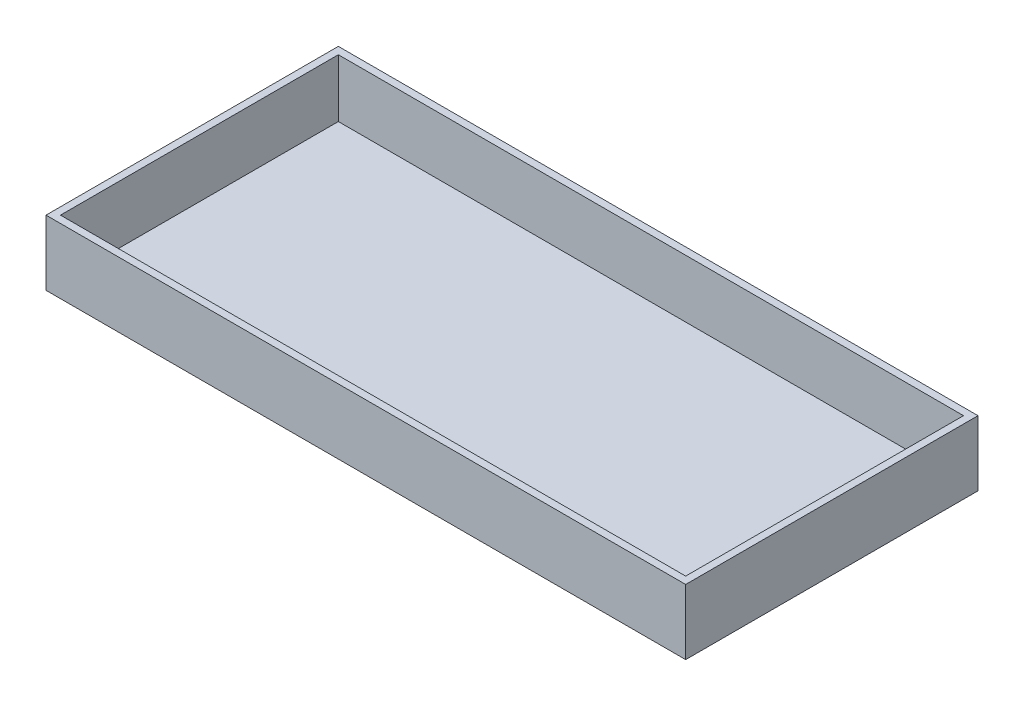
SolidWorks part; units mm, degrees
ref_plane "Front Plane" through (0, 0, 0) normal (0, 0, 1) x (1, 0, 0)
ref_plane "Top Plane" through (0, 0, 0) normal (0, 1, 0) x (1, 0, 0)
ref_plane "Right Plane" through (0, 0, 0) normal (1, 0, 0) x (0, 0, -1)
sketch "Sketch1" plane through (0, 0, 0) normal (0, 1, 0) x (1, 0, 0)
  line L0 (-110.5, -50.5) -> (-110.5, 50.5)
  line L1 (-108, -48) -> (108, -48)
  line L2 (-108, -48) -> (-108, 48)
  line L3 (-108, 48) -> (108, 48)
  line L4 (108, -48) -> (108, 48)
  line L5 (-108, -48) -> (108, 48) construction
  line L6 (-108, 48) -> (108, -48) construction
  line L7 (-110.5, 50.5) -> (110.5, 50.5)
  line L8 (110.5, -50.5) -> (110.5, 50.5)
  line L9 (-110.5, -50.5) -> (110.5, -50.5)
  point P0 (0, 0)
  dimension "D1" = 216
  dimension "D2" = 96
  dimension "D3" = 2.5
extrude "Boss-Extrude1" add sketch "Sketch1" along normal blind 20 contours L0 L9 L8 L7 L4 L1 L2 L3 region at (-108.0701, 0, 0)
extrude "Boss-Extrude2" add sketch "Sketch1<3>" against normal blind 2.5 contours L0 L7 L8 L9
sketch "Sketch1<3>" plane through (0, 0, 0) normal (0, 1, 0) x (1, 0, 0) same geometry as "Sketch1"
